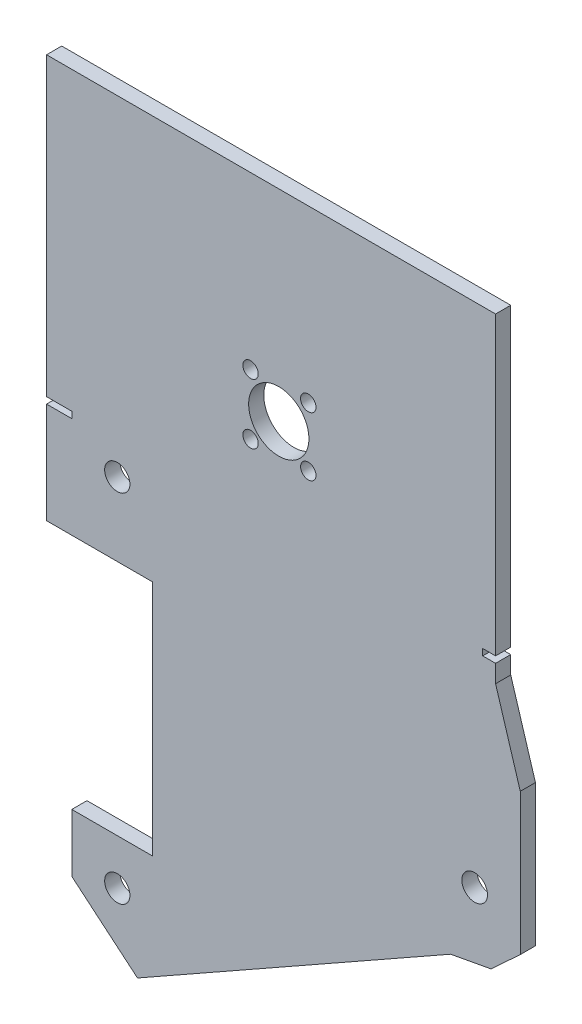
SolidWorks part; units mm, degrees
ref_plane "Front Plane" through (0, 0, 0) normal (0, 0, 1) x (1, 0, 0)
ref_plane "Top Plane" through (0, 0, 0) normal (0, 1, 0) x (1, 0, 0)
ref_plane "Right Plane" through (0, 0, 0) normal (1, 0, 0) x (0, 0, -1)
sketch "Sketch1" plane through (0, 0, 0) normal (0, 0, 1) x (1, 0, 0)
  line L0 (0, 0) -> (88.9, 0)
  line L1 (88.9, 0) -> (88.9, -3.5)
  line L2 (88.9, -3.5) -> (93.7917, -19.5)
  line L3 (93.7917, -19.5) -> (93.7917, -47.5)
  line L4 (0, 0) -> (0, -20)
  line L5 (0, -20) -> (21, -20)
  line L6 (21, -20) -> (21, -67)
  line L7 (21, -67) -> (5, -67)
  line L8 (5, -67) -> (5, -78.5)
  line L9 (5, -78.5) -> (18, -89.4083)
  line L10 (18, -89.4083) -> (80, -54.3304)
  line L11 (80, -54.3304) -> (88, -52.8477)
  line L12 (88, -52.8477) -> (93.7917, -47.5)
  dimension "D1" = 88.9
  dimension "D2" = 3.5
  dimension "D3" = 163
  dimension "D4" = 16
  dimension "D5" = 28
  dimension "D6" = 20
  dimension "D7" = 21
  dimension "D8" = 47
  dimension "D9" = 16
  dimension "D10" = 11.5
  dimension "D11" = 130
  dimension "D12" = 13
  dimension "D13" = 110.5
  dimension "D14" = 62
  dimension "D15" = 8
  dimension "D16" = 161
extrude "Boss-Extrude1" add sketch "Sketch1" along normal blind 3
sketch "Sketch2" plane through (0, 0, 0) normal (0, 1, 0) x (1, 0, 0)
  line L0 (45.8978, 14) -> (40.3978, 14) construction
  line L1 (0, -3) -> (88.9, -3)
  line L2 (0, -3) -> (0, 54)
  line L3 (0, 54) -> (88.9, 54)
  line L4 (88.9, -3) -> (88.9, 54)
  circle A0 centre (40.3978, 8.5) radius 1.5
  circle A1 centre (40.3978, 20) radius 1.5
  circle A2 centre (51.8978, 8.5) radius 1.5
  circle A3 centre (51.8978, 20) radius 1.5
  ellipse E0 centre (45.8978, 14) end of major axis (45.8978, 8) minor radius 5.5
  dimension "D9" = 3
  dimension "D10" = 3
  dimension "D11" = 3
  dimension "D12" = 3
  dimension "D1" = 88.9
  dimension "D2" = 57
  dimension "D3" = 45.8978
  dimension "D4" = 5.5
  dimension "D5" = 11.5
  dimension "D6" = 23
  dimension "D7" = 11.5
  dimension "D8" = 17
  dimension "D13" = 12
  dimension "D14" = 11
extrude "Boss-Extrude2" add sketch "Sketch2" along normal blind 3
ref_plane "Plane1" through (85.9, 0, 0) normal (1, 0, 0) x (0, 0, -1)
sketch "Sketch3" plane through (85.9, 0, 0) normal (1, 0, 0) x (0, 0, -1)
  line L0 (11.5, 0) -> (0, 0)
  line L1 (0, 0) -> (54, 0) construction
  line L2 (0, 0) -> (0, -11.5)
  line L3 (0, -19.5) -> (0, -3.5) construction
  line L4 (0, -11.5) -> (11.5, 0)
  dimension "D1" = 11.5
  dimension "D2" = 11.5
extrude "Boss-Extrude3" add sketch "Sketch3" against normal blind 84.5
sketch "Sketch4" plane through (0, 0, 0) normal (0, 0, -1) x (-1, 0, 0)
  line L0 (-1.4, -11.5) -> (-85.9, -11.5) construction
  line L1 (-81.4, -11.5) -> (-6.4, -11.5)
  line L2 (-81.4, -11.5) -> (-81.4, 0)
  line L3 (-81.4, 0) -> (-6.4, 0)
  line L4 (-6.4, -11.5) -> (-6.4, 0)
  line L5 (-50.8976, 0) -> (-85.9, 0) construction
  line L6 (-85.9, 13.7659) -> (-85.9, -13.7659) construction
  dimension "D1" = 75
  dimension "D2" = 4.5
extrude "Cut-Extrude2" cut sketch "Sketch4" along normal blind 84.5
sketch "Sketch6" plane through (0, 0, 3) normal (0, 0, 1) x (1, 0, 0)
  line L0 (0, 3) -> (0, -20) construction
  line L1 (0, 3) -> (88.9, 3) construction
  circle A0 centre (14, -76) radius 2.5
  circle A1 centre (84.763, -40.5) radius 2.54
  circle A2 centre (14, -5.5) radius 2.5
  dimension "D1" = 5
  dimension "D2" = 5
  dimension "D3" = 5.08
  dimension "D4" = 14
  dimension "D5" = 8.5
  dimension "D6" = 70.5
  dimension "D7" = 14
  dimension "D8" = 43.5
  dimension "D9" = 70.763
extrude "Cut-Extrude3" cut sketch "Sketch6" against normal blind 84.5
sketch "Sketch7" plane through (0, 0, 0) normal (0, -1, 0) x (1, 0, 0)
  line L1 (88.9, -54) -> (0, -54)
  line L2 (88.9, -54) -> (88.9, 0)
  line L3 (88.9, 0) -> (0, 0)
  line L4 (0, -54) -> (0, 0)
extrude "Cut-Extrude4" cut sketch "Sketch7" against normal through all both and the other way through all
sketch "Sketch8" plane through (0, 0, 0) normal (0, 0, -1) x (-1, 0, 0)
  line L0 (-88.9, 3) -> (0, 3) construction
  line L1 (-88.9, 3) -> (0, 3)
  line L2 (-88.9, 3) -> (-88.9, 59.896)
  line L3 (-88.9, 59.896) -> (0, 59.896)
  line L4 (0, 3) -> (0, 59.896)
  line L5 (-45.974, 20.018) -> (-40.005, 20.018) construction
  circle A0 centre (-45.974, 20.018) radius 5.969
  circle A1 centre (-40.386, 26.114) radius 1.524
  circle A2 centre (-40.386, 14.176) radius 1.524
  circle A3 centre (-51.816, 26.114) radius 1.524
  circle A4 centre (-51.816, 14.43) radius 1.524
  dimension "D8" = 11.938
  dimension "D9" = 3.048
  dimension "D10" = 3.048
  dimension "D11" = 3.048
  dimension "D12" = 3.048
  dimension "D1" = 56.896
  dimension "D2" = 88.9
  dimension "D3" = 23.114
  dimension "D4" = 11.43
  dimension "D5" = 17.018
  dimension "D6" = 11.938
  dimension "D7" = 5.588
  dimension "D13" = 45.974
  dimension "D14" = 11.43
extrude "Boss-Extrude4" add sketch "Sketch8" against normal up to surface (3 mm away) up to face at (16.5, -76, 3)
sketch "Sketch10" plane through (0, 0, 0) normal (0, 0, -1) x (-1, 0, 0)
  line L0 (-88.9, -3.5) -> (-88.9, 59.896) construction
  line L1 (0, 0) -> (-5.08, 0)
  line L2 (0, 0) -> (0, 1.27)
  line L3 (0, 1.27) -> (-5.08, 1.27)
  line L4 (-5.08, 0) -> (-5.08, 1.27)
  line L5 (-86.36, 0) -> (-88.9, 0)
  line L6 (-86.36, 0) -> (-86.36, 1.27)
  line L7 (-86.36, 1.27) -> (-88.9, 1.27)
  line L8 (-88.9, 0) -> (-88.9, 1.27)
  dimension "D1" = 5.08
  dimension "D2" = 1.27
  dimension "D3" = 2.54
  dimension "D4" = 1.27
extrude "Cut-Extrude5" cut sketch "Sketch10" against normal blind 10
